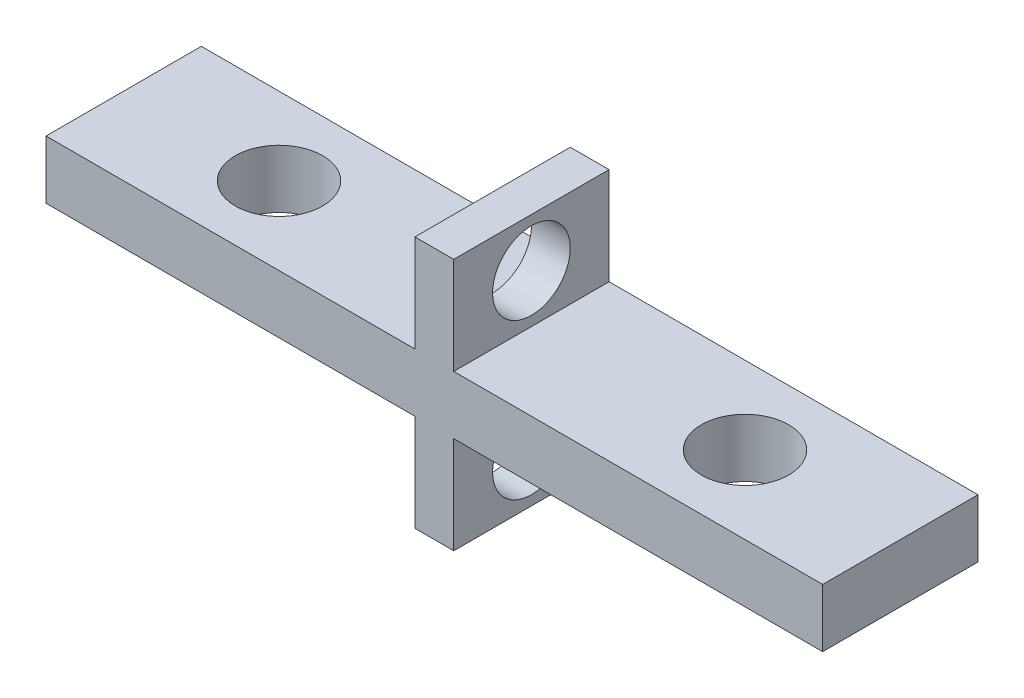
SolidWorks part; units mm, degrees
ref_plane "Front Plane" through (0, 0, 0) normal (0, 0, 1) x (1, 0, 0)
ref_plane "Top Plane" through (0, 0, 0) normal (0, 1, 0) x (1, 0, 0)
ref_plane "Right Plane" through (0, 0, 0) normal (1, 0, 0) x (0, 0, -1)
sketch "Sketch1" plane through (0, 0, 0) normal (0, 1, 0) x (1, 0, 0)
  line L1 (-7.2264, 4.3136) -> (32.7736, 4.3136)
  line L2 (-7.2264, 4.3136) -> (-7.2264, -3.6864)
  line L3 (-7.2264, -3.6864) -> (32.7736, -3.6864)
  line L4 (32.7736, 4.3136) -> (32.7736, -3.6864)
  dimension "D1" = 8
  dimension "D2" = 40
extrude "Boss-Extrude1" add sketch "Sketch1" along normal blind 3
hole_wizard "#8 Clearance Hole1" positions "3DSketch1" profile "Sketch2" hole size "#8" standard "ANSI Inch"
sketch3d "3DSketch1"
  line L0 (-7.2264, 3, -4.3136) -> (-7.2264, 3, 3.6864) construction
  line L1 (32.7736, 3, 3.6864) -> (32.7736, 3, -4.3136) construction
  line L2 (-7.2264, 3, 3.6864) -> (32.7736, 3, 3.6864) construction
  point P0 (0.7736, 3, -0.3136)
  point P2 (24.7736, 3, -0.3136)
  dimension "D1" = 8
  dimension "D2" = 8
  dimension "D3" = 4
  dimension "D4" = 4
  dimension "D5" = 24
sketch "Sketch2" plane through (0.7736, 3, -0.3136) normal (1, 0, 0) x (0, 0, 1)
  line L0 (0, 0) -> (0, 18.3507)
  line L1 (0, 18.3507) -> (2.2479, 17)
  line L2 (2.2479, 17) -> (2.2479, 0)
  line L5 (2.2479, 0) -> (0, 0)
  line L10 (0, 18.3507) -> (-2.2479, 17) construction
  line L11 (0, -6.35) -> (0, 107.95) construction
  dimension "Hole Dia." = 4.4958
  dimension "Hole Depth" = 17
  dimension "Drill Angle" = 118
sketch "Sketch5" plane through (0, 3, 0) normal (0, 1, 0) x (1, 0, 0)
  line L0 (-7.2264, -3.6864) -> (32.7736, -3.6864) construction
  line L1 (11.7736, -3.6864) -> (13.7736, -3.6864)
  line L2 (11.7736, -3.6864) -> (11.7736, 4.3136)
  line L3 (11.7736, 4.3136) -> (13.7736, 4.3136)
  line L4 (13.7736, -3.6864) -> (13.7736, 4.3136)
  line L5 (32.7736, 4.3136) -> (-7.2264, 4.3136) construction
  line L6 (-7.2264, 4.3136) -> (-7.2264, -3.6864) construction
  dimension "D1" = 19
  dimension "D2" = 19
extrude "Boss-Extrude2" add sketch "Sketch5" along normal blind 5 and the other way blind 8
sketch "Sketch6" plane through (11.7736, 0, 0) normal (-1, 0, 0) x (0, 0, 1)
  line L2 (-4.3136, 3) -> (-4.3136, 8) construction
  line L3 (-4.3136, -5) -> (-4.3136, 0) construction
  line L4 (-4.3136, 8) -> (3.6864, 8) construction
  line L5 (-4.3136, -5) -> (3.6864, -5) construction
  circle A0 centre (-0.3136, 5.5) radius 2
  circle A1 centre (-0.3136, -2.5) radius 2
  dimension "D1" = 4
  dimension "D2" = 4
  dimension "D3" = 2.5
  dimension "D4" = 2.5
extrude "Cut-Extrude1" cut sketch "Sketch6" against normal blind 2
